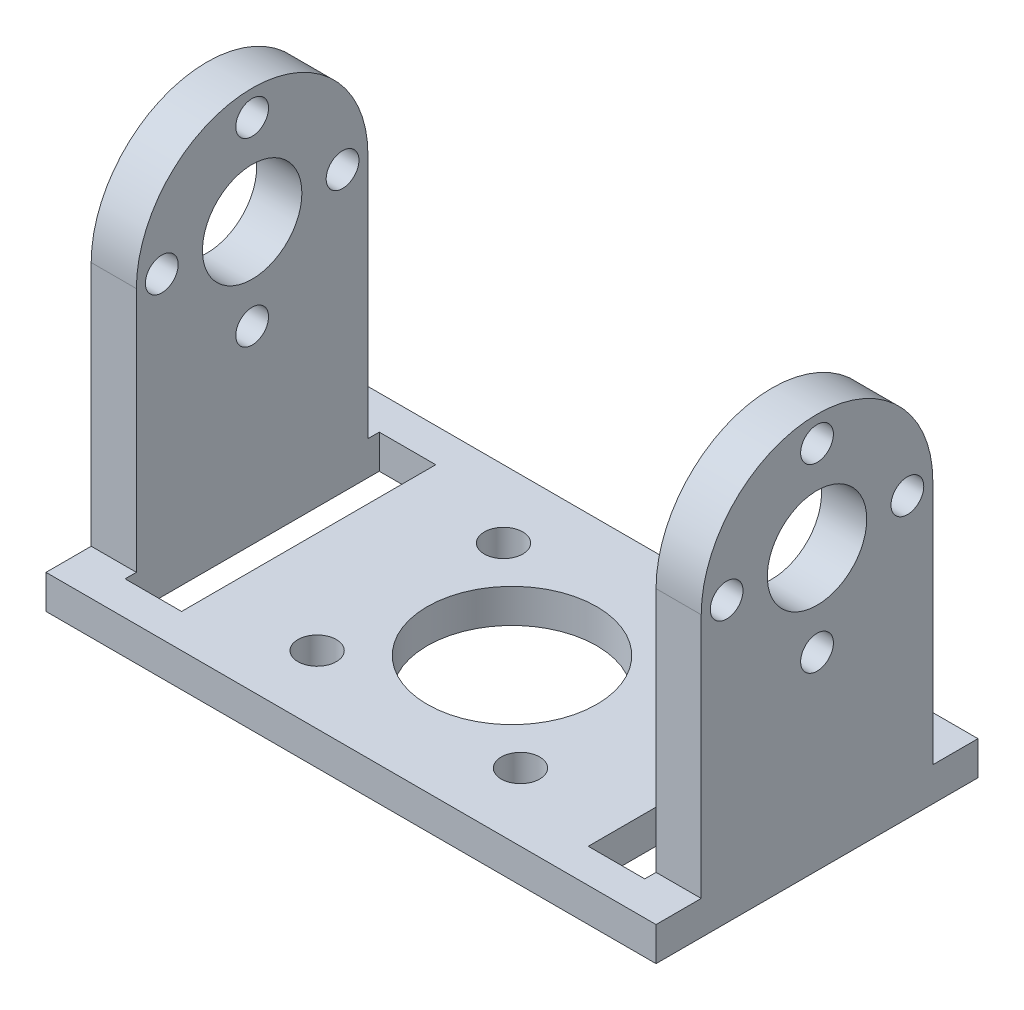
SolidWorks part; units mm, degrees
ref_plane "Front Plane" through (0, 0, 0) normal (0, 0, 1) x (1, 0, 0)
ref_plane "Top Plane" through (0, 0, 0) normal (0, 1, 0) x (1, 0, 0)
ref_plane "Right Plane" through (0, 0, 0) normal (1, 0, 0) x (0, 0, -1)
sketch "Sketch1" plane through (0, 0, 0) normal (0, 1, 0) x (1, 0, 0)
  line L0 (0, 0) -> (0, -7.6155) construction
  line L1 (-18, 14.25) -> (18, 14.25)
  line L2 (-18, 14.25) -> (-18, -14.25)
  line L3 (-18, -14.25) -> (18, -14.25)
  line L4 (18, 14.25) -> (18, -14.25)
  line L5 (0, 0) -> (0, 12.9892) construction
  line L6 (-18, 14.25) -> (-27, 14.25)
  line L7 (-18, 14.25) -> (-18, -14.25)
  line L8 (-18, -14.25) -> (-27, -14.25)
  line L9 (-27, 14.25) -> (-27, -14.25)
  line L10 (18, 14.25) -> (27, 14.25)
  line L11 (18, 14.25) -> (18, -14.25)
  line L12 (18, -14.25) -> (27, -14.25)
  line L13 (27, 14.25) -> (27, -14.25)
  line L14 (-23, 11.25) -> (-18, 11.25)
  line L15 (-23, 11.25) -> (-23, -11.25)
  line L16 (-23, -11.25) -> (-18, -11.25)
  line L17 (-18, 11.25) -> (-18, -11.25)
  line L18 (18, 11.25) -> (18, -11.25)
  line L19 (23, -11.25) -> (18, -11.25)
  line L20 (23, 11.25) -> (23, -11.25)
  line L21 (23, 11.25) -> (18, 11.25)
  circle A0 centre (0, 0) radius 7.5
  circle A1 centre (-9, 8.25) radius 1.7
  circle A2 centre (-9, -8.25) radius 1.7
  circle A3 centre (9, -8.25) radius 1.7
  circle A4 centre (9, 8.25) radius 1.7
  point P0 (0, 0)
  dimension "D3" = 9
  dimension "D4" = 8.25
  dimension "D5" = 8.25
  dimension "D6" = 9
  dimension "D7" = 9
  dimension "D9" = 15
  dimension "D1" = 36
  dimension "D2" = 28.5
  dimension "D8" = 9
  dimension "D10" = 4
  dimension "D11" = 3
  dimension "D12" = 3
  dimension "D13" = 5
extrude "Boss-Extrude2" add sketch "Sketch1" along normal blind 3 contours L6 L9 L8 L2 | L13 L10 L4 L12 | L4 L1 L2 L3 A3 A2 A1 A0 A4 region at (0, 0, -13.7908) region at (-24.0625, 0, 0) region at (24.0625, 0, 0)
sketch "Sketch2" plane through (0, 3, 0) normal (0, 1, 0) x (1, 0, 0)
  line L5 (27, 14.25) -> (27, -14.25) construction
  line L6 (27, 10.25) -> (23, 10.25)
  line L7 (27, 10.25) -> (27, -10.25)
  line L8 (27, -10.25) -> (23, -10.25)
  line L9 (23, 10.25) -> (23, -10.25)
  line L10 (27, 14.25) -> (-27, 14.25) construction
  dimension "D1" = 4
  dimension "D2" = 20.5
  dimension "D3" = 4
extrude "Boss-Extrude3" add sketch "Sketch2" along normal blind 21.75
sketch "Sketch4" plane through (27, 0, 0) normal (1, 0, 0) x (0, 0, -1)
  line L0 (-10.25, 24.75) -> (10.25, 24.75) construction
  circle A0 centre (0, 24.75) radius 10.25
  point P18 (0, 17.75)
  line M5 (10.25, 24.75) -> (-10.25, 24.75)
extrude "Boss-Extrude4" add sketch "Sketch4" against normal blind 4 contours A0 M5 | M5 | M5 | A0 M5 region at (27, 29.1002, 0) region at (27, 20.3998, 0)
ref_plane "Plane1" through (0, 0, 0) normal (1, 0, 0) x (0, 0, -1)
mirror "Mirror1" about plane through (0, 0, 0) normal (1, 0, 0) of "Boss-Extrude3", "Boss-Extrude4"
sketch "Sketch6" plane through (27, 0, 0) normal (1, 0, 0) x (0, 0, -1)
  line L0 (-10.25, 24.75) -> (10.25, 24.75) construction
  line L1 (0, 35) -> (0, 14.5) construction
  circle A6 centre (0, 24.75) radius 4.4
  circle A7 centre (0, 24.75) radius 8
  circle A8 centre (0, 32.75) radius 1.45
  circle A9 centre (8, 24.75) radius 1.45
  circle A10 centre (0, 16.75) radius 1.45
  circle A11 centre (-8, 24.75) radius 1.45
  circle A12 centre (0, 24.75) radius 10.25
  point P21 (0, 24.75)
  dimension "D1" = 8.8
  dimension "D2" = 16
  dimension "D3" = 4
  dimension "D4" = 2.9
extrude "Cut-Extrude3" cut sketch "Sketch6" against normal blind 4 contours A6 | A7 A11 | A7 A11 | A7 A10 | A7 A10 | A7 A9 | A7 A9 | A7 A8 | A7 A8 region at (27, 24.75, 0) region at (27, 24.75, -7.3615) region at (27, 24.75, -8.5911) region at (27, 32.1115, 0) region at (27, 33.3411, 0) region at (27, 16.1589, 0) region at (27, 17.3885, 0) region at (27, 24.75, 7.3615) region at (27, 24.75, 8.5911)
mirror "Mirror3" about plane through (0, 0, 0) normal (1, 0, 0) of "Cut-Extrude3"
